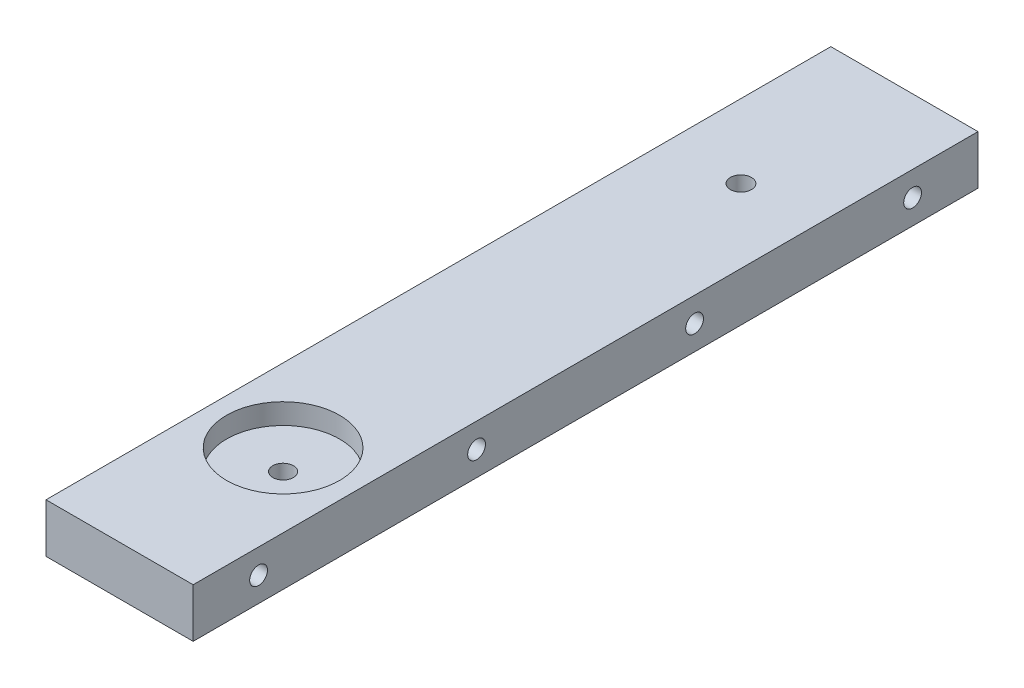
SolidWorks part; units mm, degrees
ref_plane "Front Plane" through (0, 0, 0) normal (0, 0, 1) x (1, 0, 0)
ref_plane "Top Plane" through (0, 0, 0) normal (0, 1, 0) x (1, 0, 0)
ref_plane "Right Plane" through (0, 0, 0) normal (1, 0, 0) x (0, 0, -1)
sketch "Sketch2" plane through (0, 0, 0) normal (0, 1, 0) x (1, 0, 0)
  line L0 (0, 0) -> (0, 152.4)
  line L1 (0, 152.4) -> (28.575, 152.4)
  line L2 (28.575, 152.4) -> (28.575, 0)
  line L3 (28.575, 0) -> (0, 0)
  dimension "D1" = 152.4
  dimension "D2" = 28.575
extrude "Boss-Extrude1" add sketch "Sketch2" along normal blind 9.525
sketch "Sketch3" plane through (0, 0, 0) normal (-1, 0, 0) x (0, 0, 1)
  line L3 (-152.4, 9.525) -> (0, 9.525) construction
  line L4 (-152.4, 9.525) -> (-152.4, 0) construction
  point P6 (-139.7, 4.7625)
  point P14 (-139.7, 4.7625)
  dimension "D1" = 4.7625
  dimension "D2" = 12.7
sketch "Sketch8" plane through (0, 0, 0) normal (-1, 0, 0) x (0, 0, 1)
  point P0 (-139.7, 4.7625)
hole_wizard "#5 Clearance Hole3" positions "Sketch8" profile "Sketch9" hole size "#5" standard "ANSI Inch"
sketch "Sketch9" plane through (0, 4.7625, -139.7) normal (0, 1, 0) x (0, 0, 1)
  line L0 (0, 0) -> (0, 13.7378)
  line L1 (0, 13.7378) -> (1.7272, 12.7)
  line L2 (1.7272, 12.7) -> (1.7272, 0)
  line L5 (1.7272, 0) -> (0, 0)
  line L10 (0, 13.7378) -> (-1.7272, 12.7) construction
  line L11 (0, -6.35) -> (0, 107.95) construction
  dimension "Hole Dia." = 3.4544
  dimension "Hole Depth" = 12.7
  dimension "Drill Angle" = 118
pattern_linear "LPattern1" count 4 spacing 42.3333 along (0, 0, 1) skipping (2, 0) of "#5 Clearance Hole3"
sketch "Sketch10" plane through (28.575, 0, 0) normal (1, 0, 0) x (0, 0, -1)
  line L0 (0, 9.525) -> (0, 0) construction
  line L1 (0, 9.525) -> (152.4, 9.525) construction
  point P0 (12.7, 4.7625)
  point P1 (12.7, 4.7625)
  point P5 (0, 4.7625)
  point P9 (12.7, 4.7625)
  dimension "D1" = 12.7
  dimension "D2" = 4.7625
hole_wizard "#5 Clearance Hole4" positions "Sketch10" profile "Sketch11" hole size "#5" standard "ANSI Inch"
sketch "Sketch11" plane through (28.575, 4.7625, -12.7) normal (0, 1, 0) x (0, 0, -1)
  line L0 (0, 0) -> (0, 13.7378)
  line L1 (0, 13.7378) -> (1.7272, 12.7)
  line L2 (1.7272, 12.7) -> (1.7272, 0)
  line L5 (1.7272, 0) -> (0, 0)
  line L10 (0, 13.7378) -> (-1.7272, 12.7) construction
  line L11 (0, -6.35) -> (0, 107.95) construction
  dimension "Hole Dia." = 3.4544
  dimension "Hole Depth" = 12.7
  dimension "Drill Angle" = 118
pattern_linear "LPattern2" count 4 spacing 42.3333 along (0, 0, -1) of "#5 Clearance Hole4"
sketch "Sketch12" plane through (0, 9.525, 0) normal (0, 1, 0) x (1, 0, 0)
  line L0 (28.575, 0) -> (28.575, 152.4) construction
  line L2 (0, 0) -> (28.575, 0) construction
  circle A1 centre (14.2875, 31.75) radius 10.975
  circle A2 centre (14.2875, 120.65) radius 2.05
  point P0 (14.2875, 120.65)
  point P1 (14.2875, 76.2)
  point P2 (14.2875, 31.75)
  dimension "D8" = 4.1
  dimension "D9" = 21.95
  dimension "D1" = 14.2875
  dimension "D2" = 14.2875
  dimension "D3" = 14.2875
  dimension "D4" = 76.2
  dimension "D5" = 44.45
  dimension "D6" = 44.45
sketch "Sketch13" plane through (0, 0, 0) normal (-1, 0, 0) x (0, 0, 1)
  line L2 (0, 9.525) -> (0, 0) construction
  line L3 (-152.4, 9.525) -> (0, 9.525) construction
  point P5 (-69.85, 4.7625)
  dimension "D1" = 69.85
  dimension "D2" = 4.7625
hole_wizard "#5 Clearance Hole5" positions "Sketch13" profile "Sketch14" hole size "#5" standard "ANSI Inch"
sketch "Sketch14" plane through (0, 4.7625, -69.85) normal (0, 1, 0) x (0, 0, 1)
  line L0 (0, 0) -> (0, 13.7378)
  line L1 (0, 13.7378) -> (1.7272, 12.7)
  line L2 (1.7272, 12.7) -> (1.7272, 0)
  line L5 (1.7272, 0) -> (0, 0)
  line L10 (0, 13.7378) -> (-1.7272, 12.7) construction
  line L11 (0, -6.35) -> (0, 107.95) construction
  dimension "Hole Dia." = 3.4544
  dimension "Hole Depth" = 12.7
  dimension "Drill Angle" = 118
extrude "Cut-Extrude1" cut sketch "Sketch12" against normal through all contours A2
extrude "Cut-Extrude2" cut sketch "Sketch12<4>" against normal blind 4 contours A1
sketch "Sketch12<4>" plane through (0, 9.525, 0) normal (0, 1, 0) x (1, 0, 0) same geometry as "Sketch12"
sketch "Sketch15" plane through (0, 5.525, 0) normal (0, 1, 0) x (1, 0, 0)
  circle A0 centre (14.2875, 31.75) radius 2
  dimension "D1" = 4
extrude "Cut-Extrude3" cut sketch "Sketch15" against normal through all
